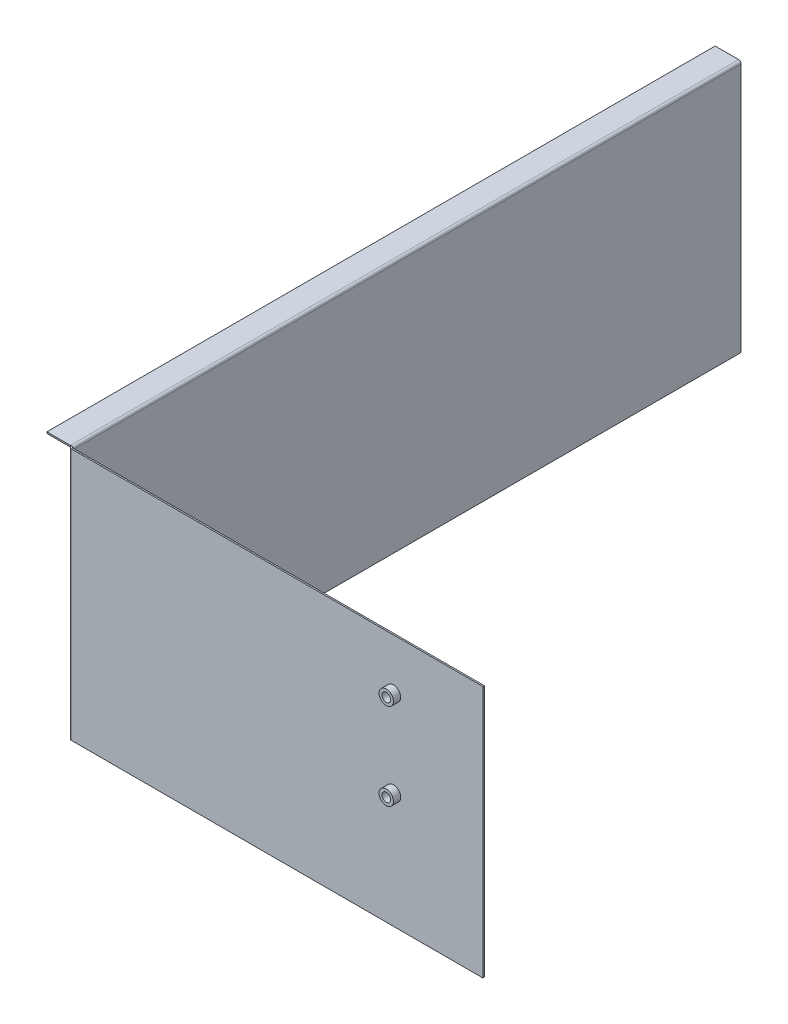
SolidWorks part; units mm, degrees
note: The reader was unsure of these and kept them because the rebuilt part matched: flange length of "Edge-Flange1", "Edge-Flange2".
ref_plane "Front Plane" through (0, 0, 0) normal (0, 0, 1) x (1, 0, 0)
ref_plane "Top Plane" through (0, 0, 0) normal (0, 1, 0) x (1, 0, 0)
ref_plane "Right Plane" through (0, 0, 0) normal (1, 0, 0) x (0, 0, -1)
sketch "Sketch1" plane through (0, 0, 0) normal (0, 0, 1) x (1, 0, 0)
  line L1 (-143.5, -87.5) -> (143.5, -87.5)
  line L2 (-143.5, -87.5) -> (-143.5, 87.5)
  line L3 (-143.5, 87.5) -> (143.5, 87.5)
  line L4 (143.5, -87.5) -> (143.5, 87.5)
  line L5 (-143.5, -87.5) -> (143.5, 87.5) construction
  line L6 (-143.5, 87.5) -> (143.5, -87.5) construction
  point P0 (0, 0)
  dimension "D1" = 287
  dimension "D2" = 175
base flange "Base-Flange1" sketch "Sketch1" thickness 1 reverse thickness direction no parameters "D1"=0.7366
sketch "Sketch6" [suppressed] plane through (0, 0, 0) normal (0, 0, 1) x (1, 0, 0)
  line L1 (-146, 110) -> (-646, 110)
  line L2 (-146, 110) -> (-146, -110)
  line L3 (-146, -110) -> (-646, -110)
  line L4 (-646, 110) -> (-646, -110)
  dimension "D1" = 500
sketch "Sketch9" [suppressed] plane through (0, 0, -1) normal (0, 0, -1) x (-1, 0, 0)
  line L0 (146, 110) -> (146, -110)
  line L1 (146, -110) -> (-146, -110) construction
  line L2 (146, -110) -> (146, 110) construction
edge flange "Edge-Flange1" sketch "Sketch12" flange angle 90 flange length 465 flange position material inside bend radius 0.7366 thickness 1 relief rectangular parameters "D6"=10
sketch "Sketch12" plane through (-143.5, 0, -1) normal (1, 0, 0) x (0, -1, 0)
  line L2 (-87.5, 0) -> (-87.5, 464)
  line L3 (-87.5, 464) -> (87.5, 464)
  line L4 (87.5, 464) -> (87.5, 0)
  line L5 (87.5, 0) -> (-87.5, 0) construction
  line L6 (87.5, 0) -> (-87.5, 0)
bend "EdgeBend1" bend radius 0.7366 bend angle 90 parameters "D5"=1
edge flange "Edge-Flange2" sketch "Sketch15" flange angle 90 flange length 18 flange position material inside bend radius 0.7366 thickness 1 relief none parameters "D6"=10
sketch "Sketch15" plane through (-143.5, 87.5, 0) normal (0, 1, 0) x (0, 0, -1)
  line L0 (465, 0) -> (1.7366, 0) construction
  line L1 (465, 0) -> (1.7366, 0)
  line L2 (1.7366, 0) -> (1.7366, 17)
  line L3 (1.7366, 17) -> (465, 17)
  line L4 (465, 17) -> (465, 0)
bend "EdgeBend2" bend radius 0.7366 bend angle 90 parameters "D5"=2
sketch "Sketch17" plane through (-143.5, 0, 0) normal (-1, 0, 0) x (0, 0, 1)
  circle A0 centre (-402.6069, 78.4539) radius 2.794
  circle A1 centre (-292.5995, 78.4539) radius 2.794
  circle A2 centre (-182.5921, 78.4539) radius 2.794
  circle A3 centre (-72.5847, 78.4539) radius 2.794
  circle A4 centre (-72.5847, 78.4539) radius 4.794
  circle A5 centre (-182.5921, 78.4539) radius 4.794
  circle A6 centre (-292.5995, 78.4539) radius 4.794
  circle A7 centre (-402.6069, 78.4539) radius 4.794
  dimension "D1" = 2
extrude "Boss-Extrude1" add sketch "Sketch17" along normal blind 18
sketch "Sketch21" plane through (0, 0, 0) normal (0, 0, 1) x (1, 0, 0)
  line L0 (143.5, -87.5) -> (143.5, 87.5) construction
  line L1 (143.5, 87.5) -> (-141.7634, 87.5) construction
  circle A0 centre (81.5, 52.5) radius 3
  circle A2 centre (81.5, 52.5) radius 5
  circle A3 centre (81.5, -7.5) radius 3
  circle A4 centre (81.5, -7.5) radius 5
  dimension "D1" = 6
  dimension "D2" = 10
  dimension "D3" = 60
  dimension "D4" = 62
  dimension "D5" = 35
extrude "Boss-Extrude2" add sketch "Sketch21" along normal blind 5
sketch "Bend-Lines1" [suppressed] plane through (0, 0, 0) normal (0, 1, 0) x (1, 0, 0)
sketch "Bounding-Box1" [suppressed] plane through (0, 0, 0) normal (0, 1, 0) x (1, 0, 0)
sheet metal parameters "Sheet-Metal1" thickness 1 parameters "D1"=0.7366
flat pattern "Flat-Pattern1" [suppressed]
sketch "Bend-Lines2" plane through (0, 0, 0) normal (0, 1, 0) x (1, 0, 0)
sketch3d "Bounding-Box2" [suppressed]
  line L0 (-146, -110, 0) -> (146, -110, 0) construction
  line L1 (-146, 110, 0) -> (146, 110, 0) construction
  line L2 (-146, -110, 0) -> (-146, 110, 0) construction
  line L3 (146, -110, 0) -> (146, 110, 0) construction
sheet metal parameters "Sheet-Metal3" thickness 1 parameters "D1"=0.7366
flat pattern "Flat-Pattern1"
sketch "Bend-Lines2" plane through (0, 0, 0) normal (0, 0, 1) x (1, 0, 0)
  line L0 (-145.2346, 87.5) -> (-145.2346, -87.5) construction
  line L1 (-145.2346, 87.5) -> (-145.2346, -87.5) construction
sketch3d "Bounding-Box2" [suppressed]
  line L0 (-603.4692, -87.5, 0) -> (146, -87.5, 0) construction
  line L1 (-603.4692, 87.5, 0) -> (146, 87.5, 0) construction
  line L2 (-603.4692, -87.5, 0) -> (-603.4692, 87.5, 0) construction
  line L3 (146, -87.5, 0) -> (146, 87.5, 0) construction
bend of the flat pattern "Flatten-<EdgeBend1>1"
sheet metal parameters "Sheet-Metal4" thickness 1 parameters "D1"=0.7366
flat pattern "Flat-Pattern1"
sketch "Bend-Lines2" plane through (0, 0, 0) normal (0, 0, 1) x (1, 0, 0)
  line L0 (-142.7346, 87.5) -> (-142.7346, -87.5) construction
  line L1 (-142.7346, 87.5) -> (-142.7346, -87.5) construction
  line L2 (-143.7058, 86.7346) -> (-606.9692, 86.7346) construction
  line L3 (-143.7058, 86.7346) -> (-606.9692, 86.7346) construction
sketch3d "Bounding-Box2" [suppressed]
  line L0 (-606.9692, -87.5, 0) -> (143.5, -87.5, 0) construction
  line L1 (-606.9692, 103.9692, 0) -> (143.5, 103.9692, 0) construction
  line L2 (-606.9692, -87.5, 0) -> (-606.9692, 103.9692, 0) construction
  line L3 (143.5, -87.5, 0) -> (143.5, 103.9692, 0) construction
bend of the flat pattern "Flatten-<EdgeBend1>1"
bend of the flat pattern "Flatten-<EdgeBend2>1"
sheet metal parameters "Sheet-Metal5" thickness 1 parameters "D1"=0.7366
flat pattern "Flat-Pattern1"
sketch "Bend-Lines2" plane through (0, 0, 0) normal (0, 0, 1) x (1, 0, 0)
  line L0 (-142.7346, 87.5) -> (-142.7346, -87.5) construction
  line L1 (-142.7346, 87.5) -> (-142.7346, -87.5) construction
  line L2 (-143.7058, 86.7346) -> (-606.9692, 86.7346) construction
  line L3 (-143.7058, 86.7346) -> (-606.9692, 86.7346) construction
sketch3d "Bounding-Box2" [suppressed]
  line L0 (-606.9692, -87.5, 0) -> (143.5, -87.5, 0) construction
  line L1 (-606.9692, 103.9692, 0) -> (143.5, 103.9692, 0) construction
  line L2 (-606.9692, -87.5, 0) -> (-606.9692, 103.9692, 0) construction
  line L3 (143.5, -87.5, 0) -> (143.5, 103.9692, 0) construction
bend of the flat pattern "Flatten-<EdgeBend1>1"
bend of the flat pattern "Flatten-<EdgeBend2>1"
sheet metal parameters "Sheet-Metal6" thickness 1 parameters "D1"=0.7366
flat pattern "Flat-Pattern1"
sketch "Bend-Lines2" plane through (0, 0, 0) normal (0, 0, 1) x (1, 0, 0)
  line L0 (-142.7346, 87.5) -> (-142.7346, -87.5) construction
  line L1 (-142.7346, 87.5) -> (-142.7346, -87.5) construction
  line L2 (-143.7058, 86.7346) -> (-606.9692, 86.7346) construction
  line L3 (-143.7058, 86.7346) -> (-606.9692, 86.7346) construction
sketch3d "Bounding-Box2" [suppressed]
  line L0 (-606.9692, -87.5, 0) -> (143.5, -87.5, 0) construction
  line L1 (-606.9692, 103.9692, 0) -> (143.5, 103.9692, 0) construction
  line L2 (-606.9692, -87.5, 0) -> (-606.9692, 103.9692, 0) construction
  line L3 (143.5, -87.5, 0) -> (143.5, 103.9692, 0) construction
bend of the flat pattern "Flatten-<EdgeBend1>1"
bend of the flat pattern "Flatten-<EdgeBend2>1"
